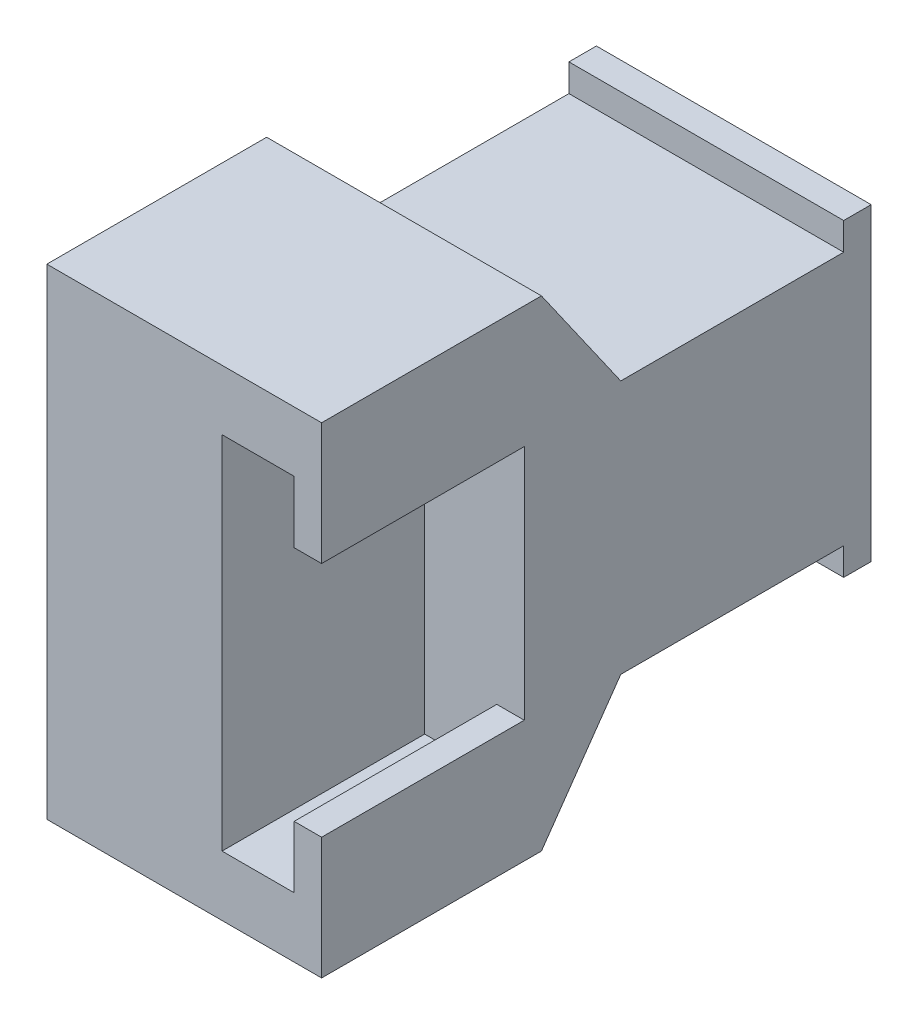
SolidWorks part; units mm, degrees
ref_plane "Ön Düzlem" through (0, 0, 0) normal (0, 0, 1) x (1, 0, 0)
ref_plane "Üst Düzlem" through (0, 0, 0) normal (0, 1, 0) x (1, 0, 0)
ref_plane "Sağ Düzlem" through (0, 0, 0) normal (1, 0, 0) x (0, 0, -1)
sketch "Çizim1" plane through (0, 0, 0) normal (0, 0, 1) x (1, 0, 0)
  line L1 (-10, 9.25) -> (10, 9.25)
  line L2 (-10, 9.25) -> (-10, -9.25)
  line L3 (-10, -9.25) -> (10, -9.25)
  line L4 (10, 9.25) -> (10, -9.25)
  line L5 (-10, 9.25) -> (10, -9.25) construction
  line L6 (-10, -9.25) -> (10, 9.25) construction
  point P0 (0, 0)
  dimension "D1" = 18.5
  dimension "D2" = 20
extrude "Yükseklik-Ekstrüzyon1" add sketch "Çizim1" along normal blind 17
sketch "Çizim2" plane through (0, -9.25, 0) normal (0, -1, 0) x (1, 0, 0)
  line L0 (-10, 17) -> (-10, 0) construction
  line L1 (-10, 2) -> (10, 2)
  line L2 (-10, 2) -> (-10, 0)
  line L3 (-10, 0) -> (10, 0)
  line L4 (10, 2) -> (10, 0)
  line L5 (-10, 2) -> (10, 0) construction
  line L6 (-10, 0) -> (10, 2) construction
  line L7 (11, 0) -> (-11, 0) construction
  point P0 (0, 1)
  point P5 (-10, 1)
  dimension "D1" = 20
  dimension "D2" = 2
  dimension "D3" = 0
  dimension "D4" = 0
extrude "Yükseklik-Ekstrüzyon2" add sketch "Çizim2" along normal blind 2
sketch "Çizim3" plane through (0, 9.25, 0) normal (0, 1, 0) x (1, 0, 0)
  line L0 (10, -17) -> (10, 0) construction
  line L1 (-10, 0) -> (10, 0)
  line L2 (-10, 0) -> (-10, -2)
  line L3 (-10, -2) -> (10, -2)
  line L4 (10, 0) -> (10, -2)
  line L5 (-10, 0) -> (10, -2) construction
  line L6 (-10, -2) -> (10, 0) construction
  line L7 (-11, 0) -> (11, 0) construction
  point P0 (0, -1)
  dimension "D1" = 20
  dimension "D2" = 2
  dimension "D3" = 0
  dimension "D4" = 0
extrude "Yükseklik-Ekstrüzyon3" add sketch "Çizim3" along normal blind 2
sketch "Çizim4" plane through (0, 0, 17) normal (0, 0, 1) x (1, 0, 0)
  line L1 (-10, 17.5) -> (10, 17.5)
  line L2 (-10, 17.5) -> (-10, -17.5)
  line L3 (-10, -17.5) -> (10, -17.5)
  line L4 (10, 17.5) -> (10, -17.5)
  line L5 (-10, 17.5) -> (10, -17.5) construction
  line L6 (-10, -17.5) -> (10, 17.5) construction
  point P0 (0, 0)
  dimension "D1" = 35
  dimension "D2" = 20
extrude "Yükseklik-Ekstrüzyon4" add sketch "Çizim4" along normal blind 23
chamfer "Pah1" distance 10 distance2 7 1 edges at (0, 17.5, 17) first distance on face at (0, 13.375, 17)
chamfer "Pah2" distance 10 distance2 7 1 edges at (0, -17.5, 17) first distance on face at (0, -13.375, 17)
sketch "Çizim5" plane through (0, 0, 40) normal (0, 0, 1) x (1, 0, 0)
  line L2 (2.75, 13.125) -> (8, 13.125)
  line L3 (2.75, 13.125) -> (2.75, -13.125)
  line L4 (2.75, -13.125) -> (8, -13.125)
  line L5 (8, 13.125) -> (8, -13.125)
  line L6 (2.75, 13.125) -> (8, -13.125) construction
  line L7 (2.75, -13.125) -> (8, 13.125) construction
  line L8 (10, -17.5) -> (10, 17.5) construction
  point P2 (5.375, 0)
  dimension "D1" = 5.25
  dimension "D2" = 26.25
  dimension "D3" = 0
  dimension "D4" = 2
extrude "Kes-Ekstrüzyon2" cut sketch "Çizim5" against normal blind 14.75
sketch "Çizim6" plane through (0, 0, 40) normal (0, 0, 1) x (1, 0, 0)
  line L0 (8, -13.125) -> (8, 13.125) construction
  line L1 (8, 8.625) -> (10, 8.625)
  line L2 (8, 8.625) -> (8, -8.625)
  line L3 (8, -8.625) -> (10, -8.625)
  line L4 (10, 8.625) -> (10, -8.625)
  line L5 (8, 8.625) -> (10, -8.625) construction
  line L6 (8, -8.625) -> (10, 8.625) construction
  line L7 (8, 13.125) -> (2.75, 13.125) construction
  line L8 (2.75, -13.125) -> (8, -13.125) construction
  point P0 (9, 0)
  dimension "D1" = 2
  dimension "D2" = 0
  dimension "D3" = 4.5
  dimension "D4" = 4.5
extrude "Kes-Ekstrüzyon3" cut sketch "Çizim6" against normal blind 14.75
